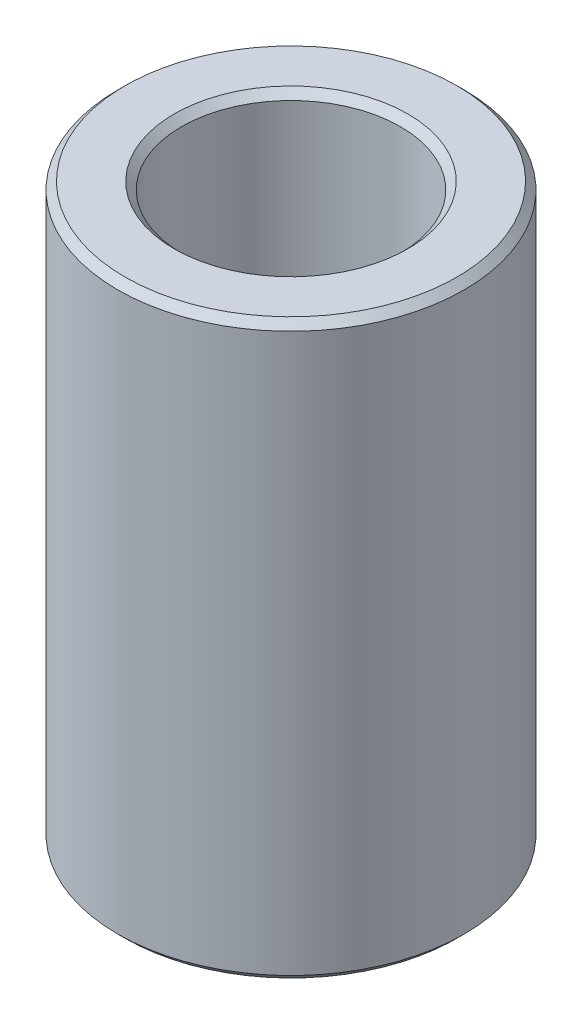
SolidWorks part; units mm, degrees
ref_plane "Front Plane" through (0, 0, 0) normal (0, 0, 1) x (1, 0, 0)
ref_plane "Top Plane" through (0, 0, 0) normal (0, 1, 0) x (1, 0, 0)
ref_plane "Right Plane" through (0, 0, 0) normal (1, 0, 0) x (0, 0, -1)
sketch "Sketch1" plane through (0, 0, 0) normal (0, 1, 0) x (1, 0, 0)
  circle A0 centre (0, 0) radius 37.5
  dimension "SLEEVE_OD" = 75
extrude "Boss-Extrude1" add sketch "Sketch1" along normal blind 123.9702
sketch "Sketch2" plane through (0, 0, 0) normal (0, 1, 0) x (1, 0, 0)
  circle A0 centre (0, 0) radius 23.7057
  dimension "BORE_D" = 47.4114
extrude "Cut-Extrude1" cut sketch "Sketch2" along normal through all
chamfer "Chamfer1" distance 1.5942 angle 45 4 edges at (0, 123.9702, 23.7057) (0, 0, 23.7057) (0, 0, 37.5) (0, 123.9702, 37.5)
